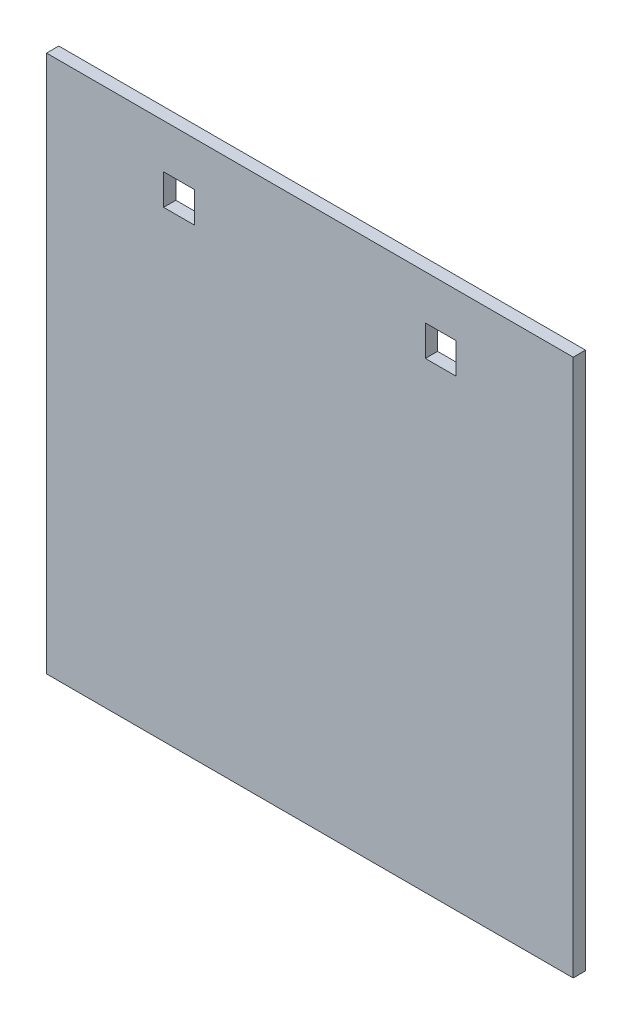
SolidWorks part; units mm, degrees
ref_plane "Front Plane" through (0, 0, 0) normal (0, 0, 1) x (1, 0, 0)
ref_plane "Top Plane" through (0, 0, 0) normal (0, 1, 0) x (1, 0, 0)
ref_plane "Right Plane" through (0, 0, 0) normal (1, 0, 0) x (0, 0, -1)
sketch "Sketch1" plane through (0, 0, 0) normal (0, 0, 1) x (1, 0, 0)
  line L1 (-68.425, 69.85) -> (68.425, 69.85)
  line L2 (-68.425, 69.85) -> (-68.425, -69.85)
  line L3 (-68.425, -69.85) -> (68.425, -69.85)
  line L4 (68.425, 69.85) -> (68.425, -69.85)
  line L5 (-68.425, 69.85) -> (68.425, -69.85) construction
  line L6 (-68.425, -69.85) -> (68.425, 69.85) construction
  point P0 (0, 0)
  dimension "D1" = 136.85
  dimension "D2" = 139.7
extrude "Boss-Extrude1" add sketch "Sketch1" along normal blind 3.18
sketch "Sketch2" plane through (0, 0, 3.18) normal (0, 0, 1) x (1, 0, 0)
  line L5 (0, 0) -> (0, 69.85) construction
  line L6 (-38, 58.35) -> (-30, 58.35)
  line L11 (-38, 58.35) -> (-38, 50.35)
  line L12 (-38, 50.35) -> (-30, 50.35)
  line L16 (-30, 58.35) -> (-30, 50.35)
  line L17 (-38, 58.35) -> (-30, 50.35) construction
  line L18 (-38, 50.35) -> (-30, 58.35) construction
  line L19 (30, 58.35) -> (38, 58.35)
  line L20 (30, 58.35) -> (30, 50.35)
  line L21 (30, 50.35) -> (38, 50.35)
  line L22 (38, 58.35) -> (38, 50.35)
  line L23 (30, 58.35) -> (38, 50.35) construction
  line L24 (30, 50.35) -> (38, 58.35) construction
  line L25 (68.425, 69.85) -> (-68.425, 69.85) construction
  point P0 (-34, 54.35)
  point P5 (34, 54.35)
  dimension "D1" = 30
  dimension "D2" = 30
  dimension "D3" = 8
  dimension "D4" = 8
  dimension "D5" = 8
  dimension "D6" = 8
  dimension "D7" = 11.5
sketch "Sketch3" plane through (0, 0, 3.18) normal (0, 0, 1) x (1, 0, 0)
  line L0 (68.425, 69.85) -> (-68.425, 69.85) construction
  line L1 (-68.425, 69.85) -> (5.895, 69.85)
  line L2 (-68.425, 69.85) -> (-68.425, 84.475)
  line L3 (-68.425, 84.475) -> (5.895, 84.475)
  line L4 (5.895, 69.85) -> (5.895, 84.475)
  line L5 (25.895, 84.475) -> (68.425, 84.475)
  line L6 (25.895, 84.475) -> (25.895, 69.85)
  line L7 (25.895, 69.85) -> (68.425, 69.85)
  line L8 (68.425, 84.475) -> (68.425, 69.85)
  circle A0 centre (15.8995, 67.85) radius 1.59
  dimension "D2" = 3.18
  dimension "D1" = 2
extrude "Cut-Extrude2" cut sketch "Sketch3" against normal blind 10
extrude "Cut-Extrude3" cut sketch "Sketch2" against normal blind 10
sketch "Sketch4" plane through (0, 0, 3.18) normal (0, 0, 1) x (1, 0, 0)
  line L0 (68.425, 69.85) -> (-68.425, 69.85) construction
  line L1 (0.5086, 69.85) -> (23.2648, 69.85)
  line L2 (0.5086, 69.85) -> (0.5086, 65.1741)
  line L3 (0.5086, 65.1741) -> (23.2648, 65.1741)
  line L4 (23.2648, 69.85) -> (23.2648, 65.1741)
extrude "Boss-Extrude2" add sketch "Sketch4" against normal blind 3.18
